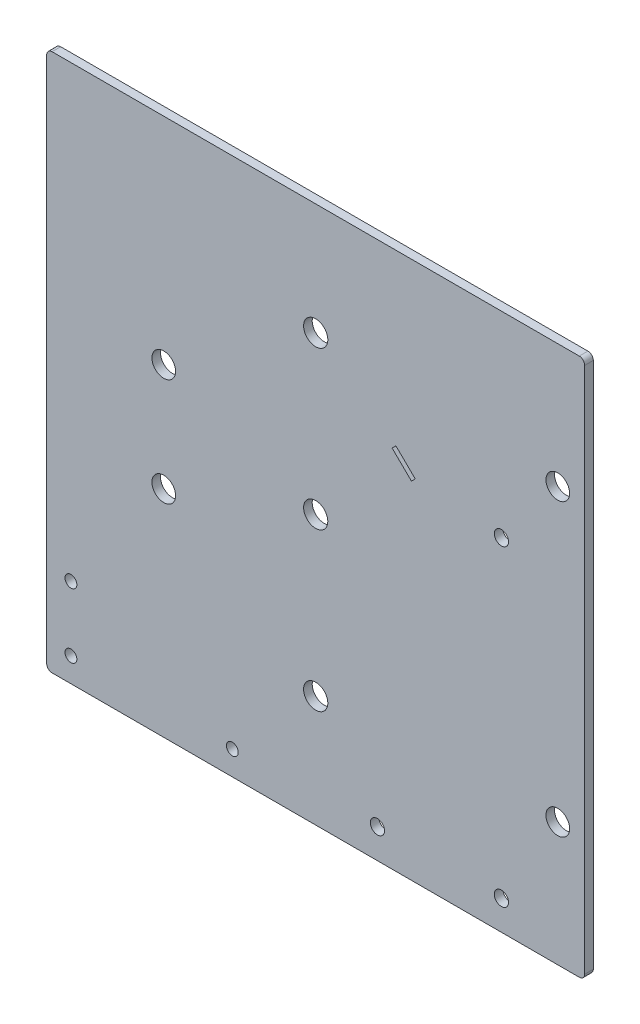
SolidWorks part; units mm, degrees
material "FR4_stuffedProtoboard"
ref_plane "Front Plane" through (0, 0, 0) normal (0, 0, 1) x (1, 0, 0)
ref_plane "Top Plane" through (0, 0, 0) normal (0, 1, 0) x (1, 0, 0)
ref_plane "Right Plane" through (0, 0, 0) normal (1, 0, 0) x (0, 0, -1)
sketch "Sketch1" plane through (0, 0, 0) normal (0, 0, 1) x (1, 0, 0)
  line L1 (-50, -50) -> (50, -50)
  line L2 (-50, -50) -> (-50, 50)
  line L3 (-50, 50) -> (50, 50)
  line L4 (50, -50) -> (50, 50)
  line L5 (-50, -50) -> (50, 50) construction
  line L6 (-50, 50) -> (50, -50) construction
  dimension "D1" = 100
extrude "Boss-Extrude1" add sketch "Sketch1" along normal blind 1.6
sketch "Sketch2" [suppressed] plane through (0, 0, 1.6) normal (0, 0, 1) x (1, 0, 0)
  circle A0 centre (0, 0) radius 50
  line M2 (50, -50) -> (50, 50)
  line M3 (50, 50) -> (-50, 50)
  line M4 (-50, 50) -> (-50, -50)
  line M5 (-50, -50) -> (50, -50)
  dimension "D1" = 100
extrude "Cut-Extrude1" [suppressed] cut sketch "Sketch2" against normal blind 1.6 contours A0 M3 M4 | A0 M4 M5 | A0 M5 M2 | A0 M2 M3
sketch "Sketch3" plane through (0, 0, 1.6) normal (0, 0, -1) x (-1, 0, 0)
  line L0 (-40, -22) -> (-50, -22) construction
  line L1 (-40, -32) -> (-40, -22) construction
  line L2 (-50, -32) -> (-40, -32) construction
  line L3 (-50, -22) -> (-50, -32) construction
  line L4 (-40, -22) -> (-50, -22)
  line L5 (-40, -32) -> (-40, -22)
  line L6 (-50, -32) -> (-40, -32)
  line L7 (-50, -22) -> (-50, -32)
  line L8 (-40, 22) -> (-40, 32) construction
  line L9 (-40, 32) -> (-50, 32) construction
  line L10 (-50, 32) -> (-50, 22) construction
  line L11 (-50, 22) -> (-40, 22) construction
  line L12 (-40, 22) -> (-40, 32)
  line L13 (-40, 32) -> (-50, 32)
  line L14 (-50, 32) -> (-50, 22)
  line L15 (-50, 22) -> (-40, 22)
  line L32 (17.2447, 25) -> (45.2447, 25) construction
  line L33 (45.2447, 25) -> (45.2447, -25) construction
  line L34 (17.2447, -25) -> (45.2447, -25) construction
  line L35 (17.2447, 25) -> (17.2447, -25) construction
  line L36 (17.2447, 25) -> (45.2447, 25)
  line L37 (45.2447, 25) -> (45.2447, -25)
  line L38 (17.2447, -25) -> (45.2447, -25)
  line L39 (17.2447, 25) -> (17.2447, -25)
  circle A3 centre (0, 0) radius 2.2479
  circle A4 centre (-34.525, -44.525) radius 1.325 construction
  circle A6 centre (-34.525, -44.525) radius 1.325
  circle A10 centre (0, -29.25) radius 2.25
  circle A11 centre (-45, -27) radius 2.2
  circle A12 centre (0, 29.25) radius 2.25
  circle A13 centre (-45, 27) radius 2.2
  circle A14 centre (-34.525, 13.525) radius 1.325 construction
  circle A15 centre (-34.525, 13.525) radius 1.325
  circle A16 centre (15.5, -45.5) radius 1.1 construction
  circle A17 centre (15.5, -45.5) radius 1.1
  circle A18 centre (45.5, -45.5) radius 1.1 construction
  circle A19 centre (45.5, -45.5) radius 1.1
  circle A20 centre (45.5, -33.5) radius 1.1 construction
  circle A21 centre (45.5, -33.5) radius 1.1
  circle A22 centre (-11.475, -44.525) radius 1.325 construction
  circle A23 centre (-11.475, -44.525) radius 1.325
  circle A25 centre (28.2447, -9.9994) radius 2.2
  circle A27 centre (28.2447, 10.0006) radius 2.2
  circle A28 centre (-45, 27) radius 2.2 construction
  circle A29 centre (-45, 27) radius 2.2
  circle A30 centre (-45, -27) radius 2.2 construction
  circle A31 centre (-45, -27) radius 2.2
  dimension "D1" = 4.4958
extrude "Cut-Extrude2" cut sketch "Sketch3" along normal through all contours A13 | A11 | A3 | A15 | A6 | A23 | A27 | A25 | A17 | A21 | A19 | A12 | A10 region at (0, 0, 1.6) region at (34.525, -44.525, 1.6) region at (45, -27, 1.6) region at (45, 27, 1.6) region at (34.525, 13.525, 1.6) region at (-15.5, -45.5, 1.6) region at (-45.5, -45.5, 1.6) region at (-45.5, -33.5, 1.6) region at (11.475, -44.525, 1.6) region at (-28.2447, -9.9994, 1.6) region at (-28.2447, 10.0006, 1.6)
sketch "Sketch4" plane through (0, 0, 1.6) normal (0, 0, 1) x (1, 0, 0)
  line L0 (38, -44.25) -> (38, -18.925) construction
  line L5 (38, -44.25) -> (38, -18.925)
  line L6 (11.75, -48) -> (34.25, -48) construction
  line L7 (11.75, -48) -> (34.25, -48)
  line L8 (8, -44.25) -> (8, 13.25) construction
  line L9 (8, -44.25) -> (8, 13.25)
  line L11 (33, -3) -> (33, -48) construction
  line L13 (34.25, 17) -> (11.75, 17)
  line L14 (38, 13.25) -> (38, -18.925)
  line L15 (-48, -48) -> (-13, -48) construction
  line L16 (-48, -48) -> (-13, -48)
  line L17 (-48, -31) -> (-48, -48) construction
  line L18 (-48, -31) -> (-48, -48)
  line L19 (-13, -40.5) -> (-13, -32.5) construction
  line L20 (-13, -40.5) -> (-13, -32.5)
  line L21 (-13, -48) -> (-13, -40.5) construction
  line L22 (-13, -48) -> (-13, -40.5)
  line L23 (-13, -32.5) -> (-13, -31) construction
  line L24 (-13, -32.5) -> (-13, -31)
  line L25 (-13, -31) -> (-48, -31) construction
  line L26 (-13, -31) -> (-48, -31)
  line L27 (-20, -34) -> (-20, -48) construction
  arc A0 (34.25, -48) -> (38, -44.25) centre (34.25, -44.25) ccw construction
  arc A1 (34.25, -48) -> (38, -44.25) centre (34.25, -44.25) ccw
  arc A2 (8, -44.25) -> (11.75, -48) centre (11.75, -44.25) ccw construction
  arc A3 (8, -44.25) -> (11.75, -48) centre (11.75, -44.25) ccw
  arc A4 (11.75, 17) -> (8, 13.25) centre (11.75, 13.25) ccw construction
  arc A5 (11.75, 17) -> (8, 13.25) centre (11.75, 13.25) ccw
  arc A6 (38, 13.25) -> (34.25, 17) centre (34.25, 13.25) ccw construction
  arc A7 (38, 13.25) -> (34.25, 17) centre (34.25, 13.25) ccw
  text T0 "Raspberry Pi Zero W" font "Century Gothic" height 2
  text T1 "Atheros" font "Century Gothic" height 2
  dimension "D1" = 5
  dimension "D2" = 20
  dimension "D3" = 3
  dimension "D4" = 7
fillet "Fillet1" radius 1 4 edges at (-50, -50, 0.8) (-50, 50, 0.8) (50, -50, 0.8) (50, 50, 0.8)
sketch "Sketch5" plane through (0, 0, 0) normal (0, 0, -1) x (-1, 0, 0)
  line L16 (-14.2075, 17.7955) -> (-17.8049, 14.2658)
  line L17 (-17.8049, 14.2658) -> (-18.5053, 14.9796)
  line L18 (-18.5053, 14.9796) -> (-14.9078, 18.5093)
  line L19 (-14.9078, 18.5093) -> (-14.2075, 17.7955)
  line L20 (-16.7065, 16.7444) -> (-13.0595, 13.0275) construction
  spline S1 degree 3 poles (-14.7296, 14.7296) (-15.9829, 13.9148) (-17.1474, 12.9675) (-18.2012, 11.9072) knots 0 0 0 0 1 1 1 1 construction
extrude "Cut-Extrude4" cut sketch "Sketch5" against normal through all contours L18 L19 L16 L17
